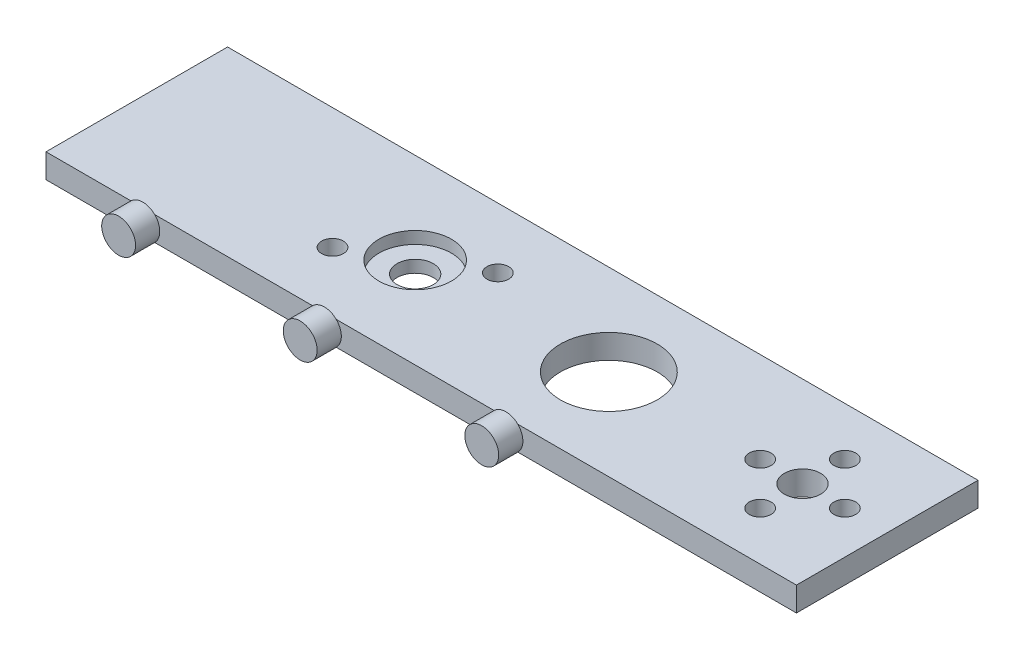
SolidWorks part; units mm, degrees
ref_plane "前视基准面" through (0, 0, 0) normal (0, 0, 1) x (1, 0, 0)
ref_plane "上视基准面" through (0, 0, 0) normal (0, 1, 0) x (1, 0, 0)
ref_plane "右视基准面" through (0, 0, 0) normal (1, 0, 0) x (0, 0, -1)
other "Configuration Table"
sketch "草图1" plane through (0, 0, 0) normal (0, 1, 0) x (1, 0, 0)
  line L0 (-31, 7.5) -> (31, 7.5)
  line L1 (31, 7.5) -> (31, -7.5)
  line L2 (31, -7.5) -> (-31, -7.5)
  line L3 (-31, -7.5) -> (-31, 7.5)
  line L4 (-31, 0) -> (31, 0) construction
  line L5 (-12.3301, -2.5) -> (-3.6699, 2.5) construction
  line L6 (-12.8083, -5.95) -> (-3.1917, -5.95) construction
  line L7 (-12.8083, 5.95) -> (-3.1917, 5.95) construction
  circle A0 centre (-8, 0) radius 1.5
  circle A1 centre (-3.6699, 2.5) radius 0.9
  circle A3 centre (-12.3301, -2.5) radius 0.9
  arc A4 (-12.8083, 5.95) -> (-12.8083, -5.95) centre (-8, 0) ccw construction
  circle A5 centre (8, 0) radius 4
  arc A6 (-3.1917, -5.95) -> (-3.1917, 5.95) centre (-8, 0) ccw construction
  circle A7 centre (24, 0) radius 1.5
  circle A8 centre (24, 0) radius 3.5 construction
  circle A9 centre (27.5, 0) radius 0.9
  circle A10 centre (24, -3.5) radius 0.9
  circle A11 centre (20.5, 0) radius 0.9
  circle A12 centre (24, 3.5) radius 0.9
  point P5 (0, 7.5)
  point P7 (-31, 0)
  dimension "D3" = 3
  dimension "D6" = 1.8
  dimension "D9" = 15.3
  dimension "D12" = 8
  dimension "D14" = 3
  dimension "D15" = 7
  dimension "D16" = 1.8
  dimension "D1" = 62
  dimension "D2" = 15
  dimension "D4" = 23
  dimension "D7" = 30
  dimension "D8" = 10
  dimension "D10" = 11.9
  dimension "D11" = 16
  dimension "D13" = 16
  dimension "D5" = 2
  dimension "D17" = 4
extrude "凸台-拉伸1" add sketch "草图1" along normal blind 2
sketch "草图2" plane through (0, 0, 7.5) normal (0, 0, 1) x (1, 0, 0)
  line L0 (-31, 1) -> (31, 1) construction
  line L1 (-31, 2) -> (-31, 0) construction
  line L2 (31, 2) -> (31, 0) construction
  circle A0 centre (-23, 1) radius 1.4
  circle A1 centre (-8, 1) radius 1.4
  circle A2 centre (7, 1) radius 1.4
  dimension "D1" = 2.8
  dimension "D2" = 2.8
  dimension "D3" = 2.8
  dimension "D4" = 15
  dimension "D5" = 15
  dimension "D6" = 8
extrude "凸台-拉伸2" add sketch "草图2" along normal blind 2
sketch "草图3" plane through (0, 2, 0) normal (0, 1, 0) x (1, 0, 0)
  text T0 "L" font "@Microsoft YaHei UI" height 3.5
sketch "草图4" plane through (0, 2, 0) normal (0, 1, 0) x (1, 0, 0)
  circle A0 centre (-8, 0) radius 3
  dimension "D1" = 6
extrude "切除-拉伸1" cut sketch "草图4" against normal blind 1
